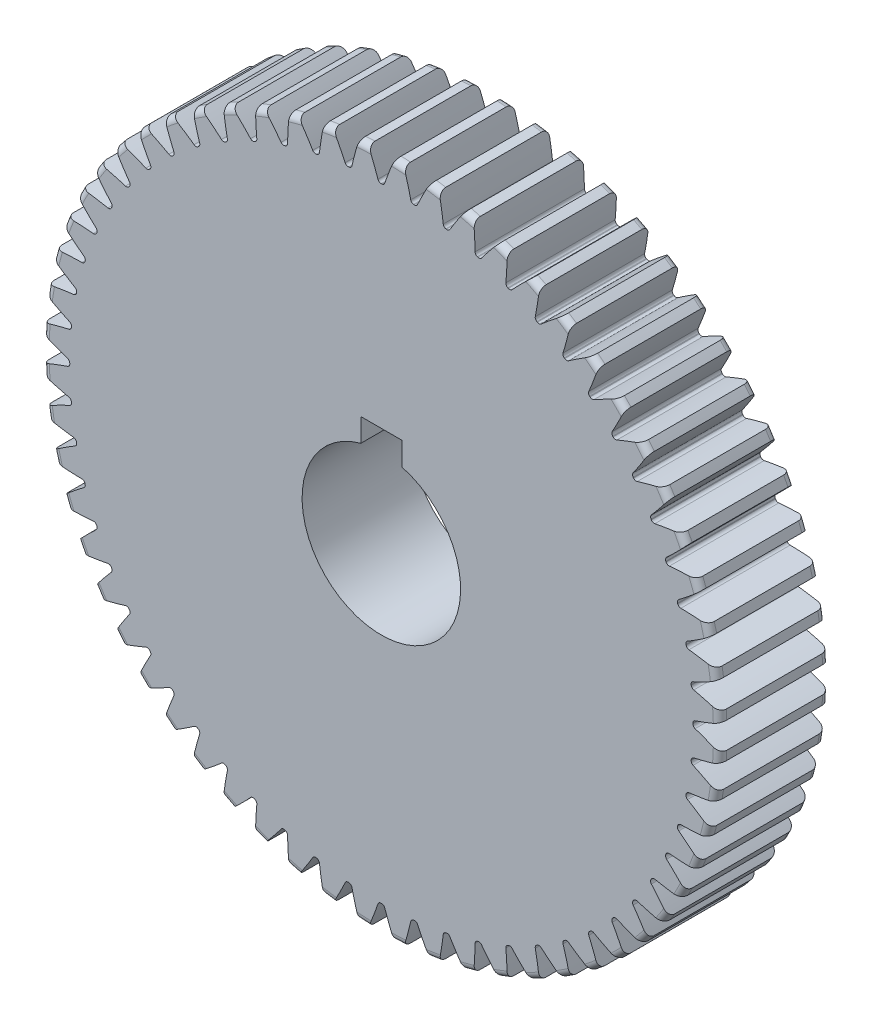
SolidWorks part; units mm, degrees
ref_plane "Front Plane" through (0, 0, 0) normal (0, 0, 1) x (1, 0, 0)
ref_plane "Top Plane" through (0, 0, 0) normal (0, 1, 0) x (1, 0, 0)
ref_plane "Right Plane" through (0, 0, 0) normal (1, 0, 0) x (0, 0, -1)
sketch "Sketch1" plane through (0, 0, 0) normal (0, 0, 1) x (1, 0, 0)
  line L0 (-762, 0) -> (762, 0) construction
  circle A0 centre (0, 0) radius 39.37 construction
  circle A1 centre (0, 0) radius 38.1 construction
  circle A2 centre (0, 0) radius 36.195 construction
  circle A3 centre (0, 0) radius 26.924 construction
  circle A4 centre (0, 0) radius 6.35 construction
  dimension "D2" = 1.27
  dimension "D3" = 3.175
  dimension "D1" = 3.175
sketch "Sketch2" plane through (0, 0, 0) normal (1, 0, 0) x (0, 0, -1)
  line L0 (0, 0) -> (-12.7, 0) construction
  line L1 (-12.7, 0) -> (-25.4, 0) construction
  dimension "Overall Width" = 25.4
  dimension "Face Width" = 12.7
sketch "Sketch4" plane through (0, 0, 0) normal (1, 0, 0) x (0, 0, -1)
  line L0 (-25.4, 6.35) -> (-25.4, 26.924)
  line L1 (-25.4, 26.924) -> (-12.7, 26.924)
  line L2 (-12.7, 26.924) -> (-12.7, 39.37)
  line L3 (-12.7, 39.37) -> (0, 39.37)
  line L4 (0, 39.37) -> (0, 6.35)
  line L5 (-12.7, 26.924) -> (-12.7, 0) construction
  line L6 (0, 39.37) -> (0, -39.37) construction
  line L7 (-12.7, 26.924) -> (0, 26.924) construction
  line L12 (-25.4, 6.35) -> (0, 6.35)
revolve "Revolve1" add sketch "Sketch4" angle 360 about L1
fillet "Fillet2" radius 0.7874 4 edges at (0, 26.924, 25.4) (0, 26.924, 12.7) (0, 39.37, 12.7) (0, 39.37, 0)
sketch "Sketch7" plane through (0, 0, 12.7) normal (0, 0, 1) x (1, 0, 0)
  line L0 (0, 0) -> (0, 39.37) construction
  line L1 (0.9973, 38.0869) -> (1.4916, 39.3417) construction
  line L3 (2.0605, 39.316) -> (1.994, 38.0478) construction
  line L4 (1.994, 38.0478) -> (1.8943, 36.1454) construction
  line L5 (0, 0) -> (1.8943, 36.1454) construction
  line L6 (0.9973, 38.0869) -> (0, 0) construction
  line L7 (0.9973, 38.0869) -> (1.0306, 39.3565) construction
  line L8 (0.9973, 38.0869) -> (0, 0) construction
  circle A0 centre (0, 0) radius 39.37 construction
  arc A1 (-0.0355, 36.195) -> (0.0355, 36.195) centre (0, 0) cw
  circle A2 centre (0, 0) radius 36.195 construction
  arc A3 (-0.9973, 38.0869) -> (0.9973, 38.0869) centre (0, 0) cw construction
  circle A4 centre (0, 0) radius 38.1 construction
  arc A5 (2.6033, 39.2838) -> (1.5172, 39.3408) centre (0, 0) ccw construction
  arc A6 (0.9973, 38.0869) -> (2.9893, 37.9826) centre (0, 0) cw construction
  arc A7 (-1.5172, 39.3408) -> (1.5172, 39.3408) centre (0, 0) cw
  arc A8 (0.3964, 36.4527) -> (1.5172, 39.3408) centre (36.4463, 24.1232) cw
  arc A9 (-0.3964, 36.4527) -> (-1.5172, 39.3408) centre (-36.4463, 24.1232) ccw
  arc A10 (-0.0355, 36.195) -> (-0.3964, 36.4527) centre (-0.0358, 36.576) cw
  arc A11 (0.0355, 36.195) -> (0.3964, 36.4527) centre (0.0358, 36.576) ccw
  point P26 (-0.3088, 36.1937)
  point P29 (0.3088, 36.1937)
  dimension "D4" = 0.381
  dimension "D5" = 38.1
  dimension "D3" = 20
  dimension "D1" = 3.9898
  dimension "D2" = 1.9949
extrude "Cut-Extrude2" cut sketch "Sketch7" against normal through all
pattern_circular "CirPattern1" count 60 over 360 about axis through (0, 0, 25.4) along (0, 0, -1) of "Cut-Extrude2"
sketch "Sketch8" plane through (0, 0, 0) normal (0, 0, -1) x (-1, 0, 0)
  circle A0 centre (0, 0) radius 9.2075
  dimension "D1" = 18.415
extrude "Cut-Extrude3" cut sketch "Sketch8" against normal up to next
sketch "Sketch9" plane through (0, 0, 25.4) normal (0, 0, 1) x (1, 0, 0)
  circle A0 centre (0, 0) radius 29.21
  dimension "D1" = 58.42
extrude "Cut-Extrude4" cut sketch "Sketch9" against normal up to surface (12.7 mm away) up to face at (0, 0, 12.7)
sketch "Sketch10" plane through (0, 0, 12.7) normal (0, 0, 1) x (1, 0, 0)
  line L0 (0, 0) -> (0, 29.2025) construction
  line L1 (-2.3812, 11.5887) -> (2.3813, 11.5887)
  line L2 (-2.3812, 11.5887) -> (-2.3812, 6.8262)
  line L3 (-2.3812, 6.8262) -> (2.3813, 6.8263)
  line L4 (2.3813, 11.5887) -> (2.3813, 6.8263)
  line L5 (0, 11.5887) -> (0, 6.8262) construction
  line L6 (0, 9.2075) -> (-19.3624, 9.2075) construction
  circle A0 centre (0, 0) radius 9.2075 construction
  circle A1 centre (0, 0) radius 9.2075
  dimension "D1" = 4.7625
  dimension "D2" = 4.7625
  dimension "D3" = 2.3812
extrude "Cut-Extrude5" cut sketch "Sketch10" against normal up to next contours A1 L4 L1 L2 region at (0, 10.3445, 12.7)
equation "\"D1@Sketch1\"=2.5*(\"Pitch Dia.@Sketch1\"/\"Number of Teeth@Sketch1\")"
equation "\"D1@CirPattern1\"=\"Number of Teeth@Sketch1\""
equation "\"D1@Fillet2\"=\"OD@Sketch1\"*.01"
equation "\"D1@Sketch7\"=3.14159*(\"Pitch Dia.@Sketch1\"/\"Number of Teeth@Sketch1\")"
equation "\"D2@Sketch7\"=\"D1@Sketch7\"/2"
equation "\"D4@Sketch7\"=\"D1@Sketch7\"*.0955"
equation "\"D5@Sketch7\"=\"Pitch Dia.@Sketch1\"/2"
